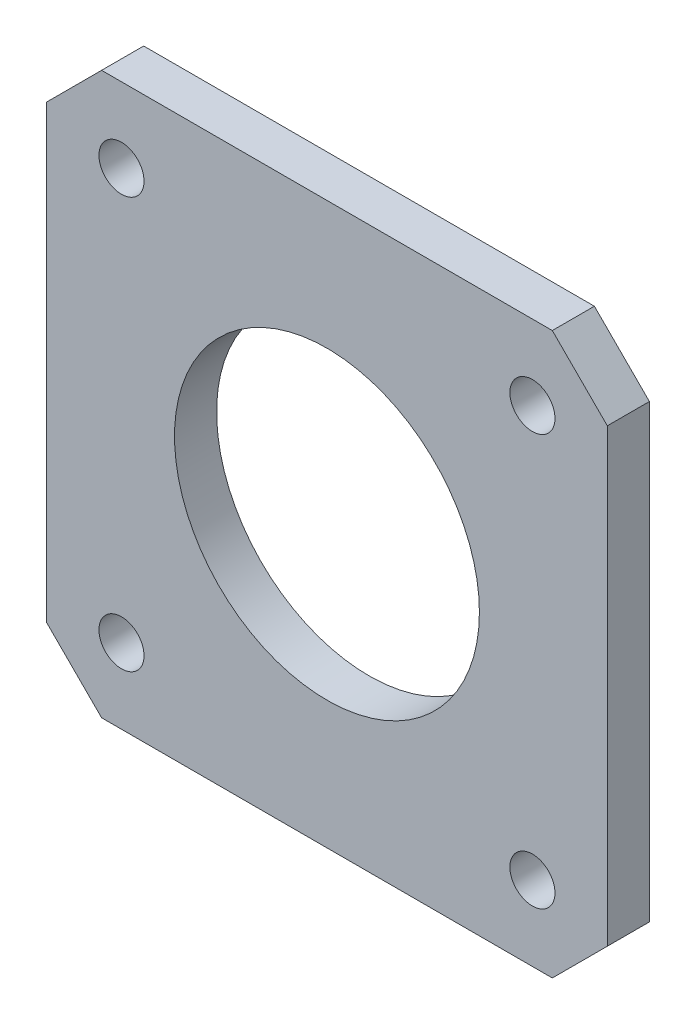
SolidWorks part; units mm, degrees
ref_plane "Front Plane" through (0, 0, 0) normal (0, 0, 1) x (1, 0, 0)
ref_plane "Top Plane" through (0, 0, 0) normal (0, 1, 0) x (1, 0, 0)
ref_plane "Right Plane" through (0, 0, 0) normal (1, 0, 0) x (0, 0, -1)
sketch "Sketch1" plane through (0, 0, 0) normal (0, 0, 1) x (1, 0, 0)
  line L0 (-17, 21.15) -> (-17, -21.15) construction
  line L1 (-17, -21.15) -> (17, -21.15)
  line L2 (-21.15, -17) -> (-21.15, 17)
  line L3 (-17, 21.15) -> (17, 21.15)
  line L4 (21.15, -17) -> (21.15, 17)
  line L5 (-19.075, -19.075) -> (19.075, 19.075) construction
  line L6 (-19.075, 19.075) -> (19.075, -19.075) construction
  line L7 (-21.15, 17) -> (21.15, 17) construction
  line L8 (17, 21.15) -> (17, -21.15) construction
  line L9 (-21.15, -17) -> (21.15, -17) construction
  line L10 (0, 17) -> (0, -17) construction
  line L11 (-17, 0) -> (17, 0) construction
  line L12 (-21.15, 17) -> (-17, 21.15)
  line L13 (17, 21.15) -> (21.15, 17)
  line L14 (21.15, -17) -> (17, -21.15)
  line L15 (-17, -21.15) -> (-21.15, -17)
  point P0 (0, 0)
  dimension "D1" = 42.3
  dimension "D2" = 34
  dimension "D3" = 34
  dimension "D4" = 42.3
extrude "Boss-Extrude1" add sketch "Sketch1" along normal blind 3.175
sketch "Sketch2" plane through (0, 0, 3.175) normal (0, 0, 1) x (1, 0, 0)
  line L1 (-15.5, -15.5) -> (15.5, -15.5) construction
  line L2 (-15.5, -15.5) -> (-15.5, 15.5) construction
  line L3 (-15.5, 15.5) -> (15.5, 15.5) construction
  line L4 (15.5, -15.5) -> (15.5, 15.5) construction
  line L5 (-15.5, -15.5) -> (15.5, 15.5) construction
  line L6 (-15.5, 15.5) -> (15.5, -15.5) construction
  circle A0 centre (0, 0) radius 11.5
  point P0 (0, 0)
  dimension "D3" = 23
  dimension "D1" = 31
  dimension "D2" = 31
extrude "Cut-Extrude1" cut sketch "Sketch2" against normal through all
hole_wizard "M3 Clearance Hole1" positions "Sketch4" profile "Sketch3" hole size "M3" standard "ANSI Metric" end condition up to next
sketch "Sketch4" plane through (0, 0, 3.175) normal (0, 0, 1) x (1, 0, 0)
  point P0 (-15.5, 15.5)
  point P2 (15.5, 15.5)
  point P4 (15.5, -15.5)
  point P6 (-15.5, -15.5)
sketch "Sketch3" plane through (-15.5, 15.5, 3.175) normal (1, 0, 0) x (0, -1, 0)
  line L0 (0, 0) -> (0, 3.175)
  line L1 (0, 3.175) -> (1.7, 3.175)
  line L2 (1.7, 3.175) -> (1.7, 0)
  line L5 (1.7, 0) -> (0, 0)
  line L11 (0, -6.35) -> (0, 107.95) construction
  dimension "Thru Hole Dia." = 3.4
  dimension "Thru Hole Depth" = 3.175
